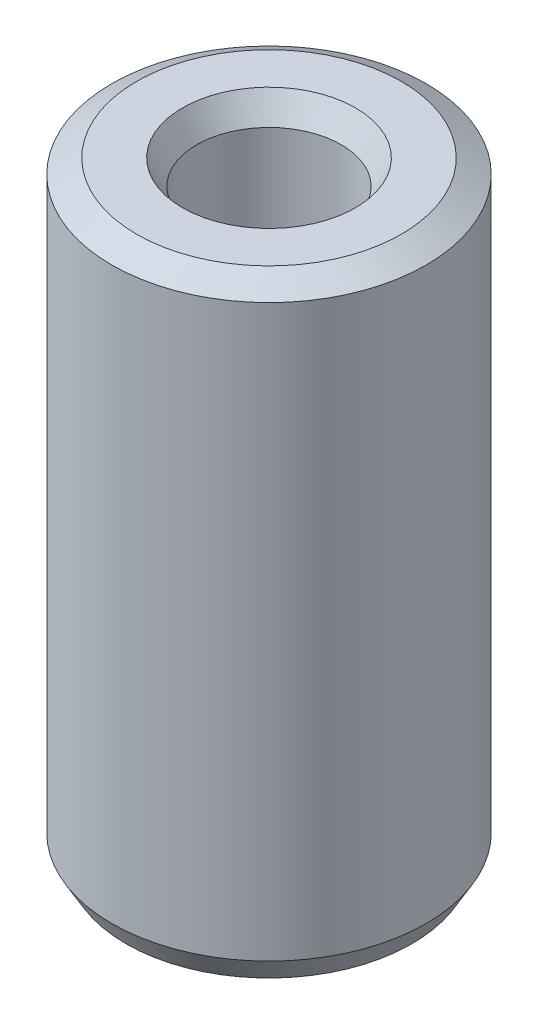
SolidWorks part; units mm, degrees
ref_plane "Front Plane" through (0, 0, 0) normal (0, 0, 1) x (1, 0, 0)
ref_plane "Top Plane" through (0, 0, 0) normal (0, 1, 0) x (1, 0, 0)
ref_plane "Right Plane" through (0, 0, 0) normal (1, 0, 0) x (0, 0, -1)
sketch "Sketch1" plane through (0, 0, 0) normal (0, 1, 0) x (1, 0, 0)
  circle A0 centre (0, 0) radius 35
  dimension "SLEEVE_OD" = 70
extrude "Boss-Extrude1" add sketch "Sketch1" along normal blind 135.7104
sketch "Sketch2" plane through (0, 0, 0) normal (0, 1, 0) x (1, 0, 0)
  circle A0 centre (0, 0) radius 16.0914
  dimension "BORE_D" = 32.1828
extrude "Cut-Extrude1" cut sketch "Sketch2" along normal through all
chamfer "Chamfer1" distance 3.1827 angle 60 4 edges at (0, 135.7104, 16.0914) (0, 0, 16.0914) (0, 0, 35) (0, 135.7104, 35) first distance on face at (0, 135.7104, 16.0914) first distance on face at (0, 0, 16.0914) first distance on face at (0, 135.7104, 35)
